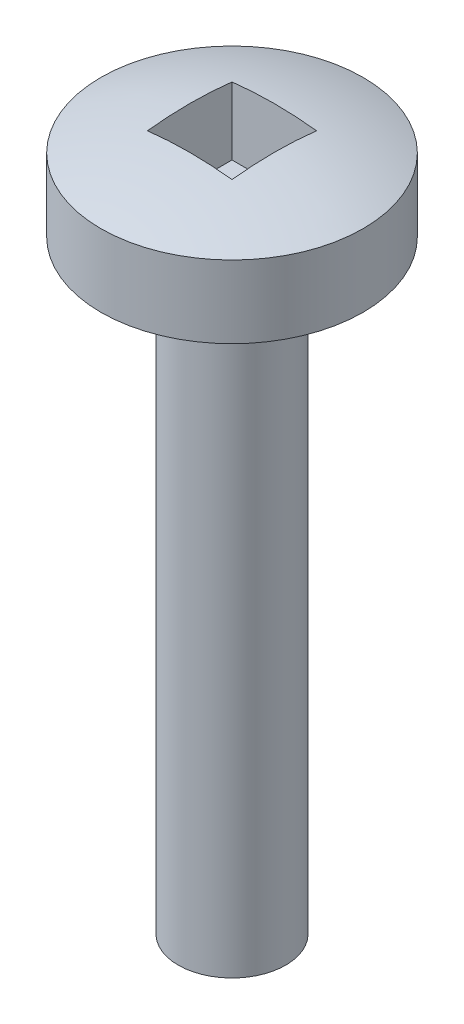
SolidWorks part; units mm, degrees
material "Cast Alloy Steel"
ref_plane "Front Plane" through (0, 0, 0) normal (0, 0, 1) x (1, 0, 0)
ref_plane "Top Plane" through (0, 0, 0) normal (0, 1, 0) x (1, 0, 0)
ref_plane "Right Plane" through (0, 0, 0) normal (1, 0, 0) x (0, 0, -1)
sketch "Sketch1" plane through (0, 0, 0) normal (0, 1, 0) x (1, 0, 0)
  circle A0 centre (0, 0) radius 1.1303
  dimension "D1" = 2.2606
extrude "threads" add sketch "Sketch1" against normal blind 12.7
sketch "Sketch2" plane through (0, 0, 0) normal (0, 1, 0) x (1, 0, 0)
  circle A0 centre (0, 0) radius 2.7559
  dimension "D1" = 5.5118
extrude "Head" add sketch "Sketch2" along normal blind 1.524
dome "HeadDome" faces to dome 1 distance 0.508 reverse direction no elliptical dome no face at (0, 1.524, 2.7559) parameters "D1"=0.508
ref_plane "DriverPlane" through (0, 2.032, 0) normal (0, 1, 0) x (1, 0, 0)
sketch "Sketch3" plane through (0, 2.032, 0) normal (0, 1, 0) x (1, 0, 0)
  line L1 (-0.889, -0.889) -> (0.889, -0.889)
  line L2 (-0.889, -0.889) -> (-0.889, 0.889)
  line L3 (-0.889, 0.889) -> (0.889, 0.889)
  line L4 (0.889, -0.889) -> (0.889, 0.889)
  line L5 (-0.889, -0.889) -> (0.889, 0.889) construction
  line L6 (-0.889, 0.889) -> (0.889, -0.889) construction
  point P0 (0, 0)
  dimension "D1" = 1.778
extrude "Driver" cut sketch "Sketch3" against normal blind 1.524
